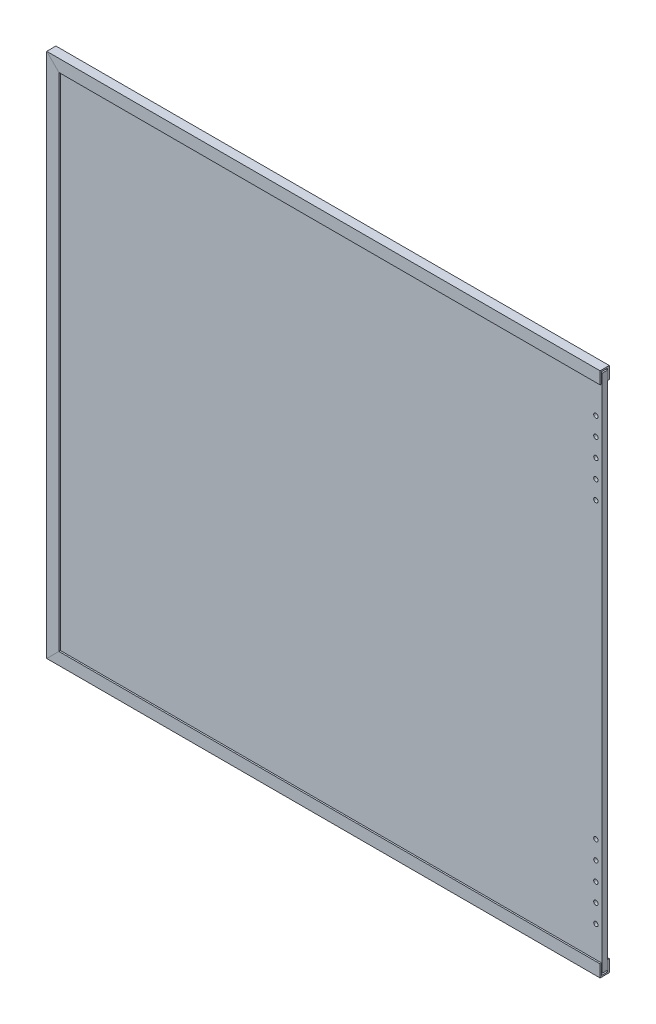
SolidWorks part; units mm, degrees
material "PC High Viscosity"
ref_plane "Front Plane" through (0, 0, 0) normal (0, 0, 1) x (1, 0, 0)
ref_plane "Top Plane" through (0, 0, 0) normal (0, 1, 0) x (1, 0, 0)
ref_plane "Right Plane" through (0, 0, 0) normal (1, 0, 0) x (0, 0, -1)
sketch "Shelf opening" plane through (0, 0, 0) normal (0, 0, 1) x (1, 0, 0)
  line L1 (0, 0) -> (577.85, 0)
  line L2 (0, 0) -> (0, 520.7)
  line L3 (0, 520.7) -> (577.85, 520.7)
  line L4 (577.85, 0) -> (577.85, 520.7)
  dimension "D1" = 577.85
  dimension "D2" = 520.7
sketch "Sketch2" plane through (0, 0, 0) normal (0, 0, 1) x (1, 0, 0)
  line L0 (577.85, 0) -> (577.85, 520.7) construction
  line L1 (3.175, 533.4) -> (577.85, 533.4)
  line L2 (3.175, 533.4) -> (3.175, -12.7)
  line L3 (3.175, -12.7) -> (577.85, -12.7)
  line L4 (577.85, 533.4) -> (577.85, -12.7)
  line L5 (0, 520.7) -> (577.85, 520.7) construction
  line L6 (0, 0) -> (0, 520.7) construction
  line L7 (0, 0) -> (577.85, 0) construction
  dimension "D1" = 12.7
  dimension "D2" = 3.175
  dimension "D3" = 12.7
extrude "Frame outer dimensions" add sketch "Sketch2" along normal mid plane 9.525
sketch "Sketch3" plane through (0, 0, 4.7625) normal (0, 0, 1) x (1, 0, 0)
  line L0 (577.85, -12.7) -> (577.85, 533.4) construction
  line L1 (577.85, 520.7) -> (15.875, 520.7)
  line L2 (577.85, 520.7) -> (577.85, 0)
  line L3 (577.85, 0) -> (15.875, 0)
  line L4 (15.875, 520.7) -> (15.875, 0)
  line L5 (577.85, 533.4) -> (3.175, 533.4) construction
  line L6 (3.175, 533.4) -> (3.175, -12.7) construction
  line L7 (3.175, -12.7) -> (577.85, -12.7) construction
  dimension "D1" = 12.7
  dimension "D2" = 12.7
  dimension "D3" = 12.7
extrude "Frame inner dimensions" cut sketch "Sketch3" against normal through all
sketch "Sketch4" plane through (0, 0, 0) normal (0, 0, 1) x (1, 0, 0)
  line L0 (577.85, 520.7) -> (577.85, 533.4) construction
  line L1 (577.85, 531.8125) -> (4.7625, 531.8125)
  line L2 (577.85, 531.8125) -> (577.85, -11.1125)
  line L3 (577.85, -11.1125) -> (4.7625, -11.1125)
  line L4 (4.7625, 531.8125) -> (4.7625, -11.1125)
  line L5 (577.85, 533.4) -> (3.175, 533.4) construction
  line L6 (3.175, 533.4) -> (3.175, -12.7) construction
  line L7 (3.175, -12.7) -> (577.85, -12.7) construction
  dimension "D1" = 1.5875
  dimension "D2" = 1.5875
  dimension "D3" = 1.5875
extrude "Frame profile" cut sketch "Sketch4" along normal offset from surface 1.5875 and the other way offset from surface 1.5875 up to face at (293.6875, 260.35, 4.7625) other way up to face at (293.6875, 260.35, -4.7625)
sketch "Frame sections" plane through (0, 0, 4.7625) normal (0, 0, 1) x (1, 0, 0)
  line L0 (3.175, 533.4) -> (15.875, 520.7)
  line L1 (3.175, -12.7) -> (15.875, 0)
split "Frame section split" trim tools "Frame sections" bodies to split 103 resulting bodies 105 106 107
sketch "Sketch5" plane through (0, 0, 0) normal (0, 0, 1) x (1, 0, 0)
  line L0 (577.85, 520.7) -> (577.85, 533.4) construction
  line L1 (577.85, 530.225) -> (6.35, 530.225)
  line L2 (577.85, 530.225) -> (577.85, -9.525)
  line L3 (577.85, -9.525) -> (6.35, -9.525)
  line L4 (6.35, 530.225) -> (6.35, -9.525)
  line L5 (4.7625, 531.8125) -> (577.85, 531.8125) construction
  line L6 (4.7625, -11.1125) -> (4.7625, 531.8125) construction
  line L7 (577.85, -11.1125) -> (4.7625, -11.1125) construction
  dimension "D1" = 1.5875
  dimension "D2" = 1.5875
  dimension "D3" = 1.5875
  dimension "D4" = 571.5
  dimension "D5" = 539.75
extrude "Door panel" add sketch "Sketch5" along normal mid plane 5.588 separate body
sketch "Hinge positions" plane through (0, 0, 2.794) normal (0, 0, 1) x (1, 0, 0)
  line L0 (577.85, -9.525) -> (577.85, 530.225) construction
  line L1 (577.85, 498.475) -> (565.15, 498.475)
  line L2 (577.85, 498.475) -> (577.85, 403.225)
  line L3 (577.85, 403.225) -> (565.15, 403.225)
  line L4 (565.15, 498.475) -> (565.15, 403.225)
  line L5 (565.15, 117.475) -> (577.85, 117.475)
  line L6 (565.15, 117.475) -> (565.15, 22.225)
  line L7 (565.15, 22.225) -> (577.85, 22.225)
  line L8 (577.85, 117.475) -> (577.85, 22.225)
  line L10 (0, 0) -> (577.85, 0) construction
  line L11 (0, 520.7) -> (577.85, 520.7) construction
  dimension "D1" = 95.25
  dimension "D2" = 12.7
  dimension "D3" = 22.225
  dimension "D4" = 22.225
  dimension "D5" = 381
sketch "Sketch8" plane through (0, 0, 2.794) normal (0, 0, 1) x (1, 0, 0)
  line L0 (565.15, 69.85) -> (577.85, 69.85) construction
  line L2 (565.15, 117.475) -> (565.15, 22.225) construction
  line L3 (577.85, 117.475) -> (577.85, 22.225) construction
  line L4 (565.15, 450.85) -> (577.85, 450.85) construction
  line L6 (565.15, 498.475) -> (565.15, 403.225) construction
  line L7 (577.85, 498.475) -> (577.85, 403.225) construction
  point P0 (571.5, 31.75)
  point P11 (571.5, 50.8)
  point P12 (571.5, 69.85)
  point P13 (571.5, 88.9)
  point P14 (571.5, 107.95)
  point P15 (571.5, 431.8)
  point P16 (571.5, 450.85)
  point P17 (571.5, 469.9)
  point P18 (571.5, 488.95)
  point P19 (571.5, 412.75)
  dimension "D3" = 19.05
  dimension "D1" = 5
  dimension "D2" = 2
hole_wizard "#8 Clearance Hole1" positions "Sketch8" profile "Sketch9" hole size "#8" standard "ANSI Inch" end condition through all
sketch "Sketch9" plane through (571.5, 31.75, 2.794) normal (1, 0, 0) x (0, -1, 0)
  line L0 (0, 0) -> (0, 7.5565)
  line L1 (0, 7.5565) -> (2.2479, 7.5565)
  line L2 (2.2479, 7.5565) -> (2.2479, 0)
  line L5 (2.2479, 0) -> (0, 0)
  line L11 (0, -6.35) -> (0, 107.95) construction
  dimension "Thru Hole Dia." = 4.4958
  dimension "Thru Hole Depth" = 7.5565
mirror "Mirror1" about plane through (0, 0, 0) normal (1, 0, 0) of bodies 105 106 107 108
delete or keep bodies "Body-Delete/Keep 1" type keep bodies bodies 105 106 107 108
delete or keep bodies "Body-Delete/Keep 2" [suppressed] type keep bodies bodies 109 110 111 112
